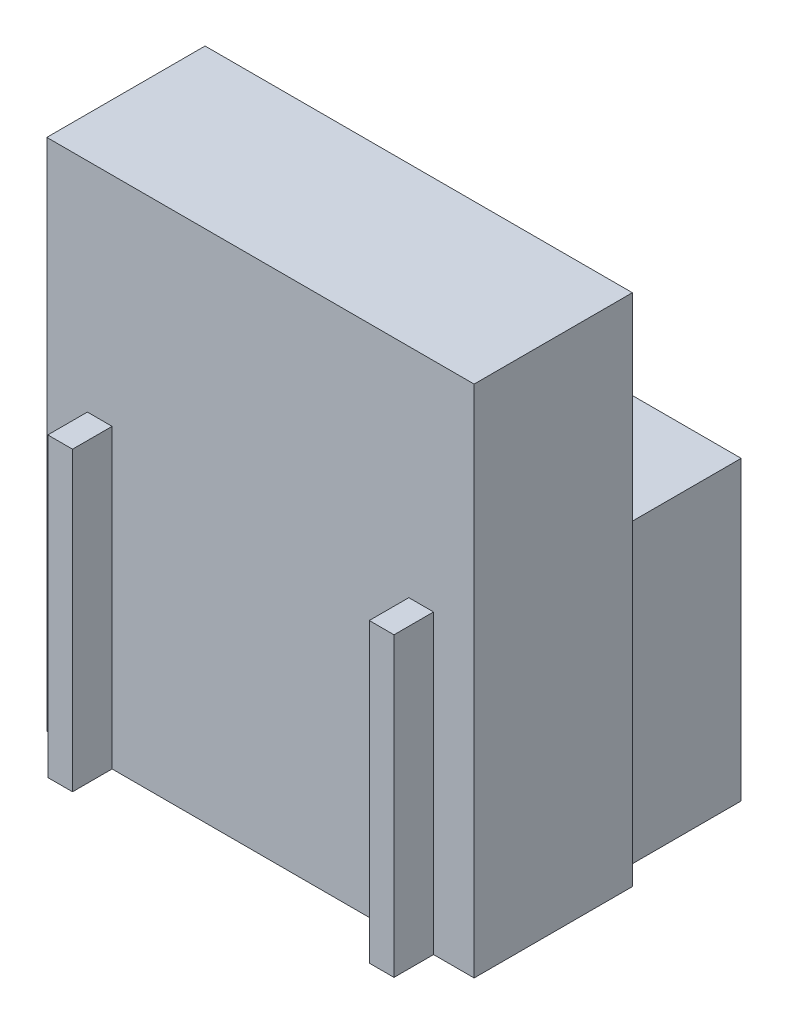
SolidWorks part; units mm, degrees
ref_plane "前视基准面" through (0, 0, 0) normal (0, 0, 1) x (1, 0, 0)
ref_plane "上视基准面" through (0, 0, 0) normal (0, 1, 0) x (1, 0, 0)
ref_plane "右视基准面" through (0, 0, 0) normal (1, 0, 0) x (0, 0, -1)
other "Configuration Table"
sketch "草图1" plane through (0, 0, 0) normal (0, 0, 1) x (1, 0, 0)
  line L0 (-21.6, 4) -> (21.6, 4)
  line L1 (21.6, -26) -> (-21.6, -26)
  line L2 (21.6, -26) -> (21.6, 26)
  line L3 (21.6, 26) -> (-21.6, 26)
  line L4 (-21.6, -26) -> (-21.6, 26)
  line L5 (21.6, -26) -> (-21.6, 26) construction
  line L6 (21.6, 26) -> (-21.6, -26) construction
  line L7 (-17.5, 4) -> (-17.5, -26)
  line L8 (-15, 4) -> (-15, -26)
  line L9 (15, 4) -> (15, -26)
  line L10 (17.5, 4) -> (17.5, -26)
  point P0 (0, 0)
  dimension "D1" = 43.2
  dimension "D2" = 52
  dimension "D3" = 30
  dimension "D4" = 30
  dimension "D5" = 35
  dimension "D6" = 2.5
  dimension "D7" = 4.1
extrude "凸台-拉伸3" add sketch "草图1" along normal blind 16 contours L7 L0 L4 L1 | L9 L0 L8 L1 | L4 L0 L2 L3 | L0 L10 L1 L2 | L8 L0 L7 L1 | L10 L0 L9 L1 region at (0, 15, 0) region at (-19.55, -11, 0) region at (-16.25, -11, 0) region at (0, -11, 0) region at (16.25, -11, 0) region at (19.55, -11, 0)
sketch "草图2" plane through (0, 0, 16) normal (0, 0, 1) x (1, 0, 0)
  line L0 (21.6, -26) -> (-21.6, -26) construction
  line L1 (-17.5, -26) -> (-15, -26)
  line L2 (-17.5, -26) -> (-17.5, 4)
  line L3 (-17.5, 4) -> (-15, 4)
  line L4 (-15, -26) -> (-15, 4)
  line L5 (-21.6, -26) -> (-21.6, 26) construction
  line L6 (15, -26) -> (17.5, -26)
  line L7 (15, -26) -> (15, 4)
  line L8 (15, 4) -> (17.5, 4)
  line L9 (17.5, -26) -> (17.5, 4)
  line L10 (21.6, -26) -> (21.6, 26) construction
  dimension "D1" = 2.5
  dimension "D2" = 2.5
  dimension "D3" = 30
  dimension "D4" = 30
  dimension "D5" = 4.1
  dimension "D6" = 4.1
extrude "凸台-拉伸4" add sketch "草图2" along normal blind 4
sketch "草图3" plane through (0, 0, 0) normal (0, 0, -1) x (-1, 0, 0)
  line L0 (-21.6, -26) -> (21.6, -26) construction
  line L1 (-19.6, -26) -> (19.6, -26)
  line L2 (-19.6, -26) -> (-19.6, 4)
  line L3 (-19.6, 4) -> (19.6, 4)
  line L4 (19.6, -26) -> (19.6, 4)
  line L5 (-21.6, -26) -> (-21.6, 26) construction
  line L6 (21.6, -26) -> (21.6, 26) construction
  dimension "D1" = 2
  dimension "D2" = 2
  dimension "D3" = 30
extrude "凸台-拉伸5" add sketch "草图3" along normal blind 13
